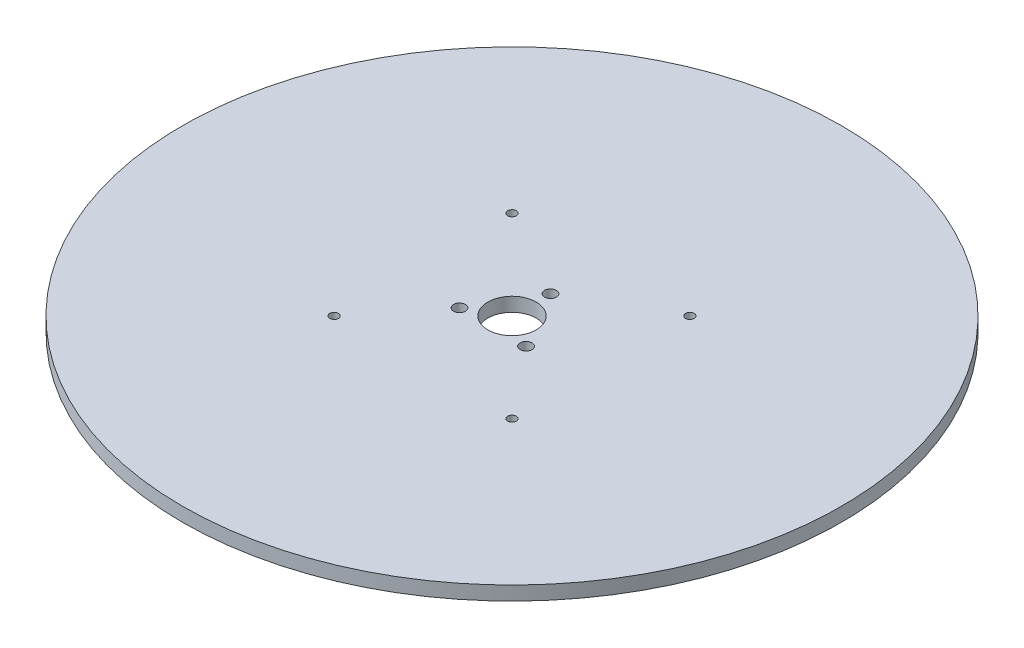
SolidWorks part; units mm, degrees
ref_plane "Front Plane" through (0, 0, 0) normal (0, 0, 1) x (1, 0, 0)
ref_plane "Top Plane" through (0, 0, 0) normal (0, 1, 0) x (1, 0, 0)
ref_plane "Right Plane" through (0, 0, 0) normal (1, 0, 0) x (0, 0, -1)
sketch "Sketch1" plane through (0, 0, 0) normal (0, 1, 0) x (1, 0, 0)
  circle A0 centre (0, 0) radius 150
  dimension "D1" = 300
extrude "Boss-Extrude1" add sketch "Sketch1" along normal blind 6.35
sketch "Sketch2" plane through (0, 6.35, 0) normal (0, 1, 0) x (1, 0, 0)
  line L0 (0, 0) -> (0, 17.5) construction
  line L1 (-40.4876, 40.4876) -> (40.4876, 40.4876) construction
  line L2 (-40.4876, 40.4876) -> (-40.4876, -40.4876) construction
  line L3 (-40.4876, -40.4876) -> (40.4876, -40.4876) construction
  line L4 (40.4876, 40.4876) -> (40.4876, -40.4876) construction
  line L5 (-40.4876, 40.4876) -> (40.4876, -40.4876) construction
  line L6 (-40.4876, -40.4876) -> (40.4876, 40.4876) construction
  line L7 (0, 0) -> (-15.1554, -8.75) construction
  line L8 (0, 0) -> (15.1554, -8.75) construction
  circle A0 centre (0, 0) radius 11
  circle A1 centre (-40.4876, 40.4876) radius 1.9844
  circle A2 centre (-40.4876, -40.4876) radius 1.9844
  circle A3 centre (40.4876, -40.4876) radius 1.9844
  circle A4 centre (40.4876, 40.4876) radius 1.9844
  circle A5 centre (0, 0) radius 17.5 construction
  circle A6 centre (0, 17.5) radius 2.7
  circle A7 centre (-15.1554, -8.75) radius 2.7
  circle A8 centre (15.1554, -8.75) radius 2.7
  dimension "D1" = 22
  dimension "D4" = 3.9688
  dimension "D5" = 35
  dimension "D8" = 5.4
  dimension "D2" = 80.9752
  dimension "D3" = 80.9752
  dimension "D6" = 120
  dimension "D7" = 120
extrude "Cut-Extrude1" cut sketch "Sketch2" against normal through all
